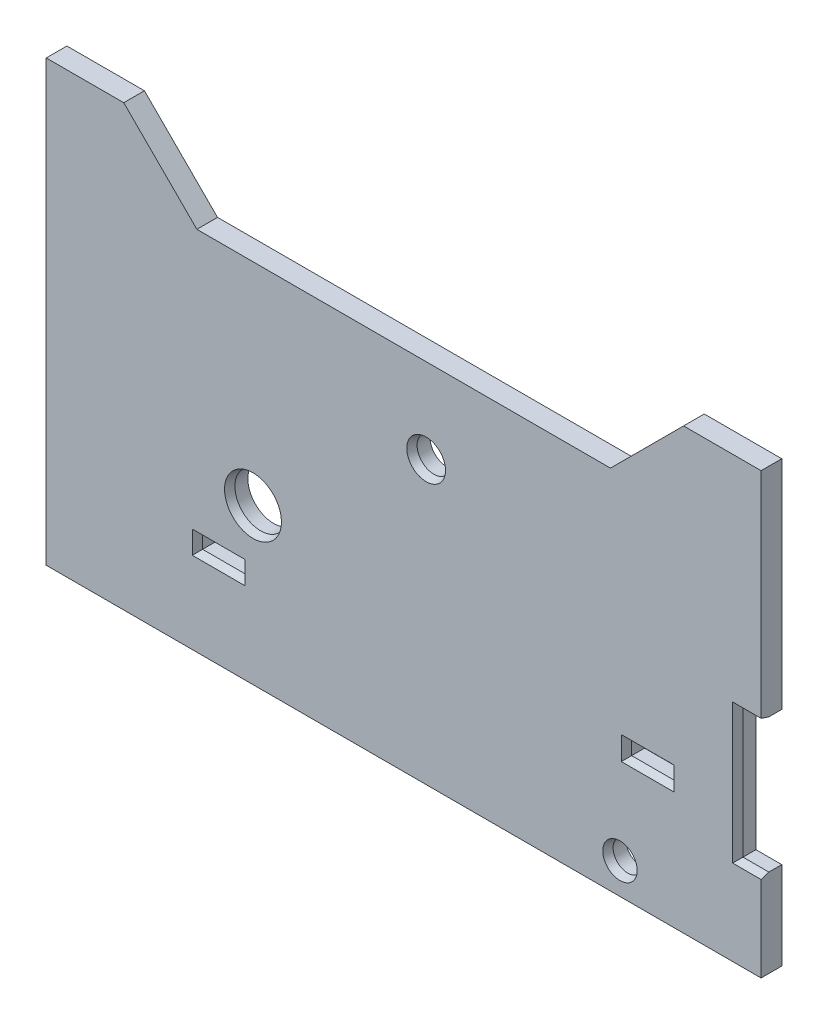
SolidWorks part; units mm, degrees
ref_plane "Front Plane" through (0, 0, 0) normal (0, 0, 1) x (1, 0, 0)
ref_plane "Top Plane" through (0, 0, 0) normal (0, 1, 0) x (1, 0, 0)
ref_plane "Right Plane" through (0, 0, 0) normal (1, 0, 0) x (0, 0, -1)
sketch "Sketch1" plane through (0, 0, 0) normal (0, 0, 1) x (1, 0, 0)
  line L2 (-86, -30) -> (-86, 30)
  line L6 (52.3, 13) -> (47.3, 13)
  line L7 (47.3, 13) -> (47.3, -13)
  line L8 (47.3, -13) -> (52.3, -13)
  line L11 (52.3, 30) -> (52.3, 13)
  line L12 (52.3, -13) -> (52.3, -30)
  line L23 (52.3, 30) -> (-86, 30)
  line L24 (25.75, -3.235) -> (34.95, -3.235)
  line L25 (25.75, -3.235) -> (25.75, -6.765)
  line L26 (25.75, -6.765) -> (34.95, -6.765)
  line L27 (34.95, -3.235) -> (34.95, -6.765)
  line L28 (25.75, -5) -> (34.95, -5) construction
  line L29 (30.35, -3.235) -> (30.35, -6.765) construction
  line L30 (-86, -30) -> (52.3, -30)
  line L31 (-48.05, -12) -> (-57.25, -12) construction
  line L32 (-57.25, -10.3) -> (-48.05, -10.3)
  line L33 (-57.25, -10.3) -> (-57.25, -13.7)
  line L34 (-57.25, -13.7) -> (-48.05, -13.7)
  line L35 (-48.05, -10.3) -> (-48.05, -13.7)
  line L36 (-52.65, -10.3) -> (-52.65, -13.83) construction
  circle A3 centre (-46, 0) radius 5
  circle A4 centre (25, -24) radius 2.83
  circle A5 centre (-12.5, 24.5) radius 3.25
  point P1 (-12, 0)
  point P33 (-52.65, -10.3)
  point P35 (-48.05, -12)
  point P36 (-57.25, -12)
  dimension "D5" = 10
  dimension "D17" = 5.66
  dimension "D25" = 6.5
  dimension "D1" = 40
  dimension "D8" = 26
  dimension "D13" = 9.2
  dimension "D14" = 3.53
  dimension "D18" = 111
  dimension "D27" = 33.5
  dimension "D28" = 24.5
  dimension "D6" = 5
  dimension "D4" = 24
  dimension "D7" = 116.35
  dimension "D9" = 60
  dimension "D3" = 138.3
  dimension "D10" = 5
  dimension "D11" = 12
  dimension "D12" = 33.35
extrude "Boss-Extrude1" add sketch "Sketch1" along normal mid plane 4
sketch "Sketch2" plane through (0, 0, 0) normal (0, 0, 1) x (1, 0, 0)
  line L0 (-86, 30) -> (52.3, 30)
  line L1 (52.3, 30) -> (52.3, 55)
  line L2 (52.3, 55) -> (37.3, 55)
  line L3 (37.3, 55) -> (23.1579, 40.8579)
  line L4 (23.1579, 40.8579) -> (-56.8579, 40.8579)
  line L5 (-56.8579, 40.8579) -> (-71, 55)
  line L6 (-71, 55) -> (-86, 55)
  line L7 (-86, 55) -> (-86, 30)
  dimension "D1" = 25
  dimension "D2" = 15
  dimension "D3" = 20
  dimension "D4" = 135
extrude "Boss-Extrude2" add sketch "Sketch2" along normal mid plane 4
sketch "Sketch3" plane through (0, 0, 2) normal (0, 0, 1) x (1, 0, 0)
  line L0 (25.75, -5) -> (34.95, -5) construction
  line L1 (25.75, -3.235) -> (25.75, -6.765) construction
  line L2 (34.95, -6.765) -> (34.95, -3.235) construction
  line L3 (30.35, -3.235) -> (30.35, -6.765) construction
  line L4 (34.95, -3.235) -> (25.75, -3.235) construction
  line L5 (25.75, -6.765) -> (34.95, -6.765) construction
  line L6 (-57.25, -12) -> (-48.05, -12) construction
  line L7 (-57.25, -10.3) -> (-57.25, -13.7) construction
  line L8 (-48.05, -13.7) -> (-48.05, -10.3) construction
  line L9 (-52.65, -10.3) -> (-52.65, -13.7) construction
  line L10 (-48.05, -10.3) -> (-57.25, -10.3) construction
  line L11 (-57.25, -13.7) -> (-48.05, -13.7) construction
sketch "Sketch4" plane through (47.3, 0, 0) normal (1, 0, 0) x (0, 0, -1)
  line L0 (-2, 0) -> (2, 0) construction
  line L1 (-2, -13) -> (-2, 13) construction
  line L2 (2, -13) -> (2, 13) construction
chamfer "Chamfer1" distance 0.5 distance2 1.5 11 edges at (27.83, -24, 2) (30.35, -6.765, 2) (25.75, -5, 2) (30.35, -3.235, 2) (34.95, -5, 2) (-48.05, -12, 2) (-52.65, -13.7, 2) (-57.25, -12, 2) (-52.65, -10.3, 2) (-41, 0, 2) (-9.25, 24.5, 2) first distance on face at (-41, 0, 2)
chamfer "Chamfer2" distance 1.5 distance2 0.5 3 edges at (49.8, -13, 2) (47.3, 0, 2) (49.8, 13, 2) first distance on face at (49.8, -13, 0) first distance on face at (47.3, 0, 0) first distance on face at (49.8, 13, 0)
equation "\"back_boost\"= 7"
equation "\"D18@Sketch1\"=\"back_boost\"+104.00mm"
equation "\"D1@Sketch1\"=33.00mm+\"back_boost\""
equation "\"D7@Sketch1\"=109.35mm+\"back_boost\""
equation "\"D3@Sketch1\"=131.30mm+\"back_boost\""
equation "\"D12@Sketch1\"=\"back_boost\"+26.35mm"
equation "\"pin_hole_height\"=9.2"
equation "\"D13@Sketch1\"=\"pin_hole_height\""
equation "\"pin_hole_width\"=3.53"
equation "\"D14@Sketch1\"=\"pin_hole_width\""
